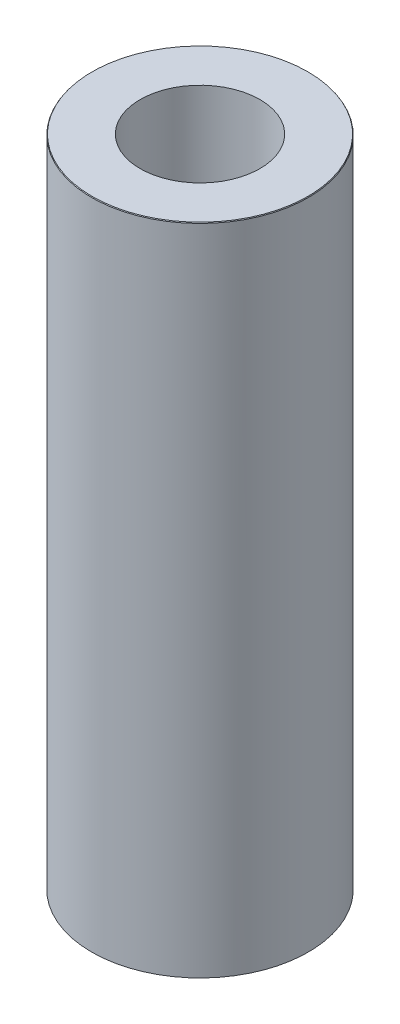
SolidWorks part; units mm, degrees
ref_plane "Front Plane" through (0, 0, 0) normal (0, 0, 1) x (1, 0, 0)
ref_plane "Top Plane" through (0, 0, 0) normal (0, 1, 0) x (1, 0, 0)
ref_plane "Right Plane" through (0, 0, 0) normal (1, 0, 0) x (0, 0, -1)
sketch "Sketch1" plane through (0, 0, 0) normal (0, 1, 0) x (1, 0, 0)
  circle A0 centre (0, 0) radius 35
  dimension "SHAFT_OD" = 70
extrude "Boss-Extrude1" add sketch "Sketch1" along normal blind 211.4404
sketch "Sketch2" plane through (0, 0, 0) normal (0, 1, 0) x (1, 0, 0)
  circle A0 centre (0, 0) radius 19.3419
  dimension "BORE_D" = 38.6837
extrude "Cut-Extrude1" cut sketch "Sketch2" along normal through all
chamfer "Chamfer1" distance 0.2551 angle 30 2 edges at (0, 211.4404, 35) (0, 0, 35) first distance on face at (0, 211.4404, 35) first distance on face at (0, 0, 19.3419)
